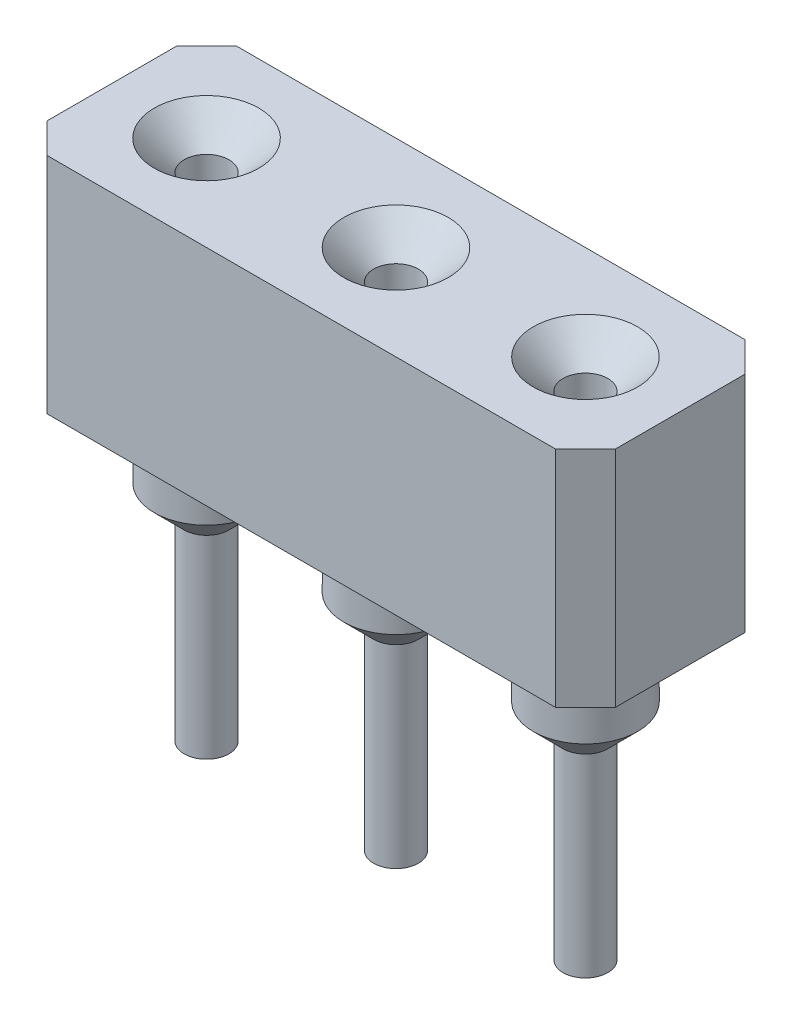
SolidWorks part; units mm, degrees
ref_plane "Plan de face" through (0, 0, 0) normal (0, 0, 1) x (1, 0, 0)
ref_plane "Plan de dessus" through (0, 0, 0) normal (0, 1, 0) x (1, 0, 0)
ref_plane "Plan de droite" through (0, 0, 0) normal (1, 0, 0) x (0, 0, -1)
sketch "Esquisse1" plane through (0, 0, 0) normal (0, 1, 0) x (1, 0, 0)
  line L0 (-3.81, -1.27) -> (3.81, 1.27) construction
  line L1 (-3.81, -1.27) -> (3.81, -1.27)
  line L2 (-3.81, -1.27) -> (-3.81, 1.27)
  line L3 (-3.81, 1.27) -> (3.81, 1.27)
  line L4 (3.81, -1.27) -> (3.81, 1.27)
  dimension "D1" = 2.54
  dimension "D2" = 7.62
extrude "Boss.-Extru.1" add sketch "Esquisse1" along normal blind 3
sketch "Esquisse2" plane through (0, 3, 0) normal (0, 1, 0) x (1, 0, 0)
  line L0 (-3.81, 1.27) -> (-3.81, -1.27) construction
  line L1 (-3.81, -1.27) -> (3.81, -1.27) construction
  circle A0 centre (-2.54, 0) radius 0.3
  circle A2 centre (0, 0) radius 0.3
  circle A3 centre (2.54, 0) radius 0.3
  dimension "D2" = 0.6
  dimension "D1" = 1.27
  dimension "D3" = 1.27
  dimension "D4" = 3
extrude "Enlèv. mat.-Extru.1" cut sketch "Esquisse2" against normal blind 2
sketch "Esquisse3" plane through (0, 0, 0) normal (0, 1, 0) x (1, 0, 0)
  line L0 (-3.81, 1.27) -> (-3.81, -1.27) construction
  line L1 (3.81, 1.27) -> (-3.81, 1.27) construction
  circle A0 centre (-2.54, 0) radius 0.7
  circle A2 centre (0, 0) radius 0.7
  circle A3 centre (2.54, 0) radius 0.7
  dimension "D2" = 1.4
  dimension "D1" = 1.27
  dimension "D3" = 1.27
  dimension "D4" = 3
extrude "Boss.-Extru.2" add sketch "Esquisse3" against normal blind 1
sketch "Esquisse4" plane through (0, -1, 0) normal (0, -1, 0) x (1, 0, 0)
  circle A0 centre (-2.54, 0) radius 0.3
  circle A2 centre (-2.54, 0) radius 0.7 construction
  circle A4 centre (0, 0) radius 0.3
  circle A5 centre (2.54, 0) radius 0.3
  dimension "D1" = 0.6
  dimension "D2" = 3
extrude "Boss.-Extru.3" add sketch "Esquisse4" along normal blind 3
chamfer "Chanfrein1" distance 0.4 angle 45 10 edges at (3.81, 1.5, -1.27) (3.81, 1.5, 1.27) (-3.81, 1.5, -1.27) (-3.81, 1.5, 1.27) (-2.54, 3, 0.3) (-2.54, -1, -0.3) (2.54, 3, 0.3) (0, 3, 0.3) (2.54, -1, -0.3) (0, -1, -0.3)
